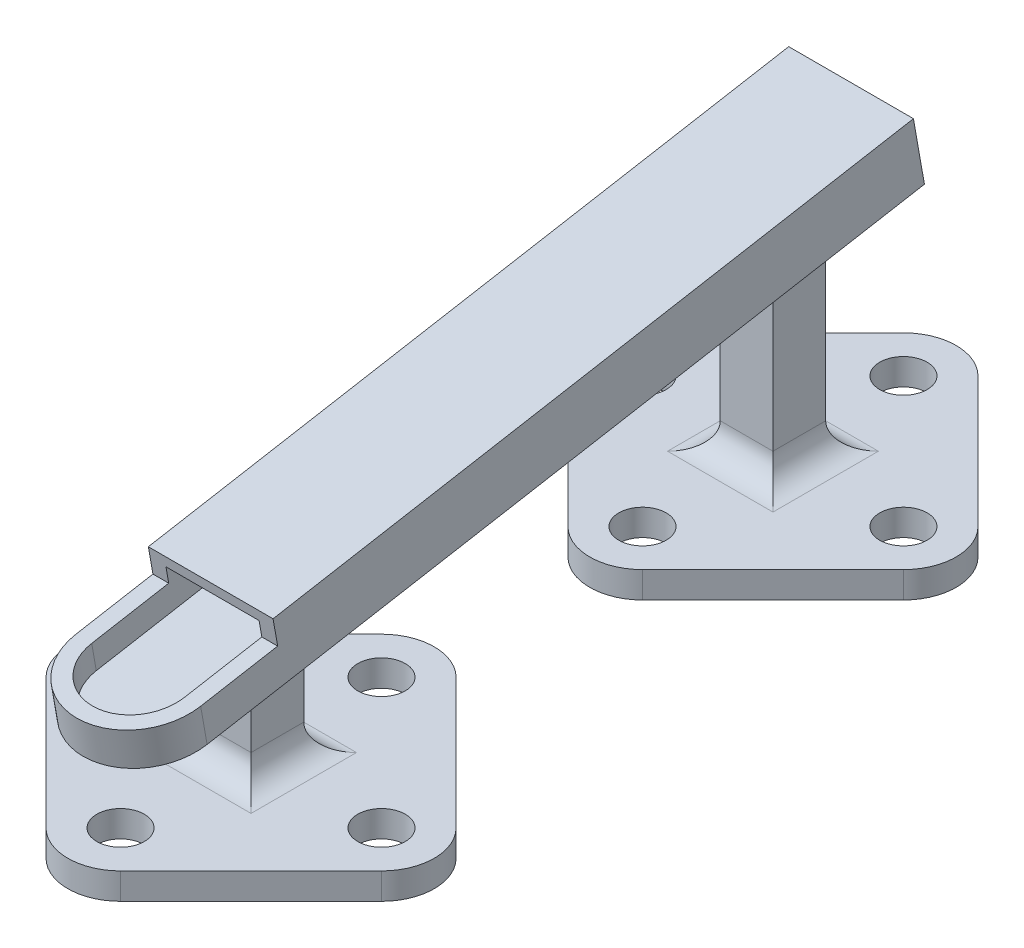
SolidWorks part; units mm, degrees
ref_plane "Front" through (0, 0, 0) normal (0, 0, 1) x (1, 0, 0)
ref_plane "Top" through (0, 0, 0) normal (0, 1, 0) x (1, 0, 0)
ref_plane "Right" through (0, 0, 0) normal (1, 0, 0) x (0, 0, -1)
ref_axis "Axis1" through (0, 55, 0) along (0, -1, 0)
ref_axis "Axis2" through (88.99, 0, 0) along (-1, 0, 0)
ref_axis "Axis3" through (0, 0, 55) along (0, 0, -1)
sketch "Sketch1" plane through (0, 0, 0) normal (0, 1, 0) x (1, 0, 0)
  line L0 (-24.75, 0) -> (0, 24.75) construction
  line L9 (-24.75, 0) -> (0, -24.75) construction
  line L11 (0, 24.75) -> (24.75, 0) construction
  line L12 (0, -24.75) -> (24.75, 0) construction
  line L13 (-24.75, 0) -> (24.75, 0) construction
  line L14 (0, 24.75) -> (0, -24.75) construction
  line L15 (-31.8211, 7.0711) -> (-7.0711, 31.8211)
  line L16 (7.0711, 31.8211) -> (31.8211, 7.0711)
  line L17 (7.0711, -31.8211) -> (31.8211, -7.0711)
  line L18 (-31.8211, -7.0711) -> (-7.0711, -31.8211)
  line L19 (0, -38.8921) -> (38.8921, 0) construction
  line L20 (-38.8921, 0) -> (0, -38.8921) construction
  line L21 (0, 38.8921) -> (38.8921, 0) construction
  line L22 (-38.8921, 0) -> (0, 38.8921) construction
  arc A4 (7.0711, -31.8211) -> (-7.0711, -31.8211) centre (0, -24.75) cw
  arc A5 (31.8211, 7.0711) -> (31.8211, -7.0711) centre (24.75, 0) cw
  arc A6 (-7.0711, 31.8211) -> (7.0711, 31.8211) centre (0, 24.75) cw
  arc A7 (-31.8211, 7.0711) -> (-31.8211, -7.0711) centre (-24.75, 0) ccw
  circle A8 centre (0, 24.75) radius 4.5
  circle A9 centre (24.75, 0) radius 4.5
  circle A10 centre (0, -24.75) radius 4.5
  circle A11 centre (-24.75, 0) radius 4.5
  point P1 (0, 0)
  dimension "D3" = 10
  dimension "D4" = 9
  dimension "D1" = 49.5
  dimension "D2" = 10
extrude "Boss-Extrude1" add sketch "Sketch1" along normal mid plane 5
ref_plane "Plane1" through (0, 0, 49.5) normal (0, 0, 1) x (1, 0, 0)
mirror "Mirror3" about plane through (0, 0, 49.5) normal (0, 0, 1) of bodies 101
sketch "Sketch2" plane through (0, 0, 0) normal (1, 0, 0) x (0, 0, -1)
  line L0 (-106.0711, 2.5) -> (-130.8211, 2.5) construction
  line L1 (-104, 2.5) -> (-94, 2.5)
  line L2 (-104, 2.5) -> (-104, 47.5)
  line L3 (-104, 47.5) -> (-94, 47.5)
  line L4 (-94, 2.5) -> (-94, 47.5)
  line L5 (-106.0711, -2.5) -> (-91.9289, -2.5) construction
  line L6 (-67.1789, -2.5) -> (-91.9289, -2.5) construction
  point P8 (-99, -2.5)
  point P9 (-99, 47.5)
  dimension "D1" = 10
  dimension "D2" = 50
extrude "Boss-Extrude2" add sketch "Sketch2" along normal mid plane 10 separate body
mirror "Mirror5" about plane through (0, 0, 49.5) normal (0, 0, 1) of bodies 103
sketch "Sketch3" plane through (0, 0, 0) normal (1, 0, 0) x (0, 0, -1)
  line L0 (-104, 22.5) -> (5, 41.7196)
  line L1 (-67.1789, -2.5) -> (-91.9289, -2.5) construction
  line L2 (-104, 47.5) -> (-104, 2.5) construction
  line L3 (-106.0711, 2.5) -> (-130.8211, 2.5) construction
  line L4 (5, 47.5) -> (5, 2.5) construction
  point P6 (-104, 22.5)
  dimension "D1" = 10
  dimension "D2" = 20
extrude "Cut-Extrude1" cut sketch "Sketch3" against normal through all both and the other way through all
sketch "Sketch4" plane through (0, 0, 0) normal (1, 0, 0) x (0, 0, -1)
  line L0 (-130.8211, 17.7707) -> (16.9001, 43.8179)
  line L1 (-130.8211, 17.7707) -> (-131.1684, 19.7403)
  line L2 (16.9001, 43.8179) -> (16.5528, 45.7876)
  line L3 (-131.1684, 19.7403) -> (16.5528, 45.7876)
  line L4 (-5, 39.9564) -> (5, 41.7196) construction
  dimension "D1" = 2
  dimension "D2" = 150
extrude "Boss-Extrude3" add sketch "Sketch4" along normal mid plane 23.66 separate body
combine bodies "Combine1" operation type add bodies to combine 102 106
combine bodies "Combine2" operation type add bodies to combine 107 101
fillet "Fillet1" radius 5 4 edges at (0, 2.5, 94) (-5, 2.5, 99) (0, 2.5, 104) (5, 2.5, 99)
fillet "Fillet2" radius 5 4 edges at (0, 2.5, 5) (0, 2.5, -5) (-5, 2.5, 0) (5, 2.5, 0)
sketch "Sketch5" plane through (0, 41.5762, 7.331) normal (0, 0.9848, 0.1736) x (1, 0, 0)
  line L0 (11.83, -113.9177) -> (0, -113.9177) construction
  line L1 (11.83, 24.2523) -> (11.83, -125.7477) construction
  line L2 (0, -113.9177) -> (0, -125.7477) construction
  line L3 (11.83, -125.7477) -> (-11.83, -125.7477) construction
  line L4 (-11.83, -113.9177) -> (-11.83, -125.7477)
  line L5 (-11.83, -125.7477) -> (0, -125.7477)
  line L6 (0, -125.7477) -> (11.83, -125.7477)
  line L7 (11.83, -125.7477) -> (11.83, -113.9177)
  circle A0 centre (0, -113.9177) radius 8.73 construction
  circle A1 centre (0, -113.9177) radius 8.83
  circle A2 centre (0, -113.9177) radius 11.83
  point P12 (-16.4373, -129.5378)
  line M3 (-11.83, 24.2523) -> (-11.83, -125.7477)
  line M4 (-11.83, -125.7477) -> (11.83, -125.7477)
  line M5 (11.83, -125.7477) -> (11.83, 24.2523)
  dimension "D1" = 17.46
  dimension "D2" = 0.1
  dimension "D3" = 3
extrude "Cut-Extrude4" cut sketch "Sketch5" against normal up to next (2 mm away) contours A2 M3 M4 | A2 M4 M5 region at (-9.1876, 20.1992, 128.5661) region at (9.1876, 20.1992, 128.5661)
sketch "Sketch6" plane through (0, 41.5762, 7.331) normal (0, 0.9848, 0.1736) x (1, 0, 0)
  line L6 (8.83, -113.9177) -> (8.83, 21.2523)
  line L7 (8.83, 21.2523) -> (-8.83, 21.2523)
  line L8 (-8.83, 21.2523) -> (-8.83, -113.9177)
  line L9 (8.83, -113.9177) -> (8.83, 21.2523)
  line L10 (8.83, 21.2523) -> (-8.83, 21.2523)
  line L11 (-8.83, 21.2523) -> (-8.83, -113.9177)
  line L12 (11.83, -113.9177) -> (11.83, 24.2523)
  line L13 (11.83, 24.2523) -> (-11.83, 24.2523)
  line L14 (-11.83, 24.2523) -> (-11.83, -113.9177)
  line L15 (11.83, -113.9177) -> (11.83, 24.2523)
  line L16 (11.83, 24.2523) -> (-11.83, 24.2523)
  line L17 (-11.83, 24.2523) -> (-11.83, -113.9177)
  arc A2 (-8.83, -113.9177) -> (8.83, -113.9177) centre (0, -113.9177) ccw
  arc A3 (-8.83, -113.9177) -> (8.83, -113.9177) centre (0, -113.9177) ccw
  arc A4 (-11.83, -113.9177) -> (11.83, -113.9177) centre (0, -113.9177) ccw
  arc A5 (-11.83, -113.9177) -> (11.83, -113.9177) centre (0, -113.9177) ccw
  dimension "D1" = 3
  dimension "D2" = 0
extrude "Boss-Extrude4" add sketch "Sketch6" along normal blind 5
sketch "Sketch7" plane through (0, 46.5002, 8.1992) normal (0, 0.9848, 0.1736) x (1, 0, 0)
  line L1 (-11.83, -99.0877) -> (-8.83, -99.0877)
  line L2 (-8.83, 21.2523) -> (-8.83, -113.9177) construction
  line L3 (11.83, -113.9177) -> (11.83, 24.2523)
  line L4 (11.83, 24.2523) -> (-11.83, 24.2523)
  line L5 (-11.83, 24.2523) -> (-11.83, -113.9177)
  line L6 (11.83, -99.0877) -> (11.83, 24.2523)
  line L7 (11.83, 24.2523) -> (-11.83, 24.2523)
  line L8 (-11.83, 24.2523) -> (-11.83, -99.0877)
  line L10 (8.83, -113.9177) -> (8.83, 21.2523) construction
  line L11 (8.83, -99.0877) -> (11.83, -99.0877)
  line L12 (8.83, 21.2523) -> (-8.83, 21.2523) construction
  line L13 (8.83, 21.2523) -> (-8.83, 21.2523)
  line L14 (-8.83, 21.2523) -> (-8.83, -99.0877)
  line L15 (8.83, -99.0877) -> (8.83, 21.2523)
  arc A1 (-11.83, -113.9177) -> (11.83, -113.9177) centre (0, -113.9177) ccw
  arc A4 (-8.83, -113.9177) -> (8.83, -113.9177) centre (0, -113.9177) ccw construction
  dimension "D2" = 6
  dimension "D1" = 0
extrude "Boss-Extrude5" add sketch "Sketch7" along normal blind 5
sketch "Sketch8" plane through (0, 0, 0) normal (1, 0, 0) x (0, 0, -1)
  line L0 (-106.6499, 34.2179) -> (-106.3026, 32.2483)
  line L1 (-106.6499, 34.2179) -> (-105.7816, 29.2938) construction
  line L2 (-106.3026, 32.2483) -> (15.1636, 53.666)
  line L3 (16.9001, 43.8179) -> (14.8163, 55.6356) construction
  line L4 (15.1636, 53.666) -> (14.8163, 55.6356)
  line L5 (14.8163, 55.6356) -> (-106.6499, 34.2179)
  dimension "D1" = 2
extrude "Boss-Extrude6" add sketch "Sketch8" along normal up to next and the other way up to next
sketch "Sketch9" plane through (0, 3.6904, -20.9294) normal (0, -0.1736, 0.9848) x (1, 0, 0)
  line L4 (8.83, 50.2176) -> (-8.83, 50.2176)
  line L5 (-8.83, 50.2176) -> (-8.83, 42.2176)
  line L6 (-8.83, 42.2176) -> (8.83, 42.2176)
  line L7 (8.83, 42.2176) -> (8.83, 50.2176)
  line L8 (8.83, 50.2176) -> (-8.83, 50.2176)
  line L9 (-8.83, 50.2176) -> (-8.83, 42.2176)
  line L10 (-8.83, 42.2176) -> (8.83, 42.2176)
  line L11 (8.83, 42.2176) -> (8.83, 50.2176)
  dimension "D1" = 0
extrude "Cut-Extrude5" cut sketch "Sketch9" against normal through all
